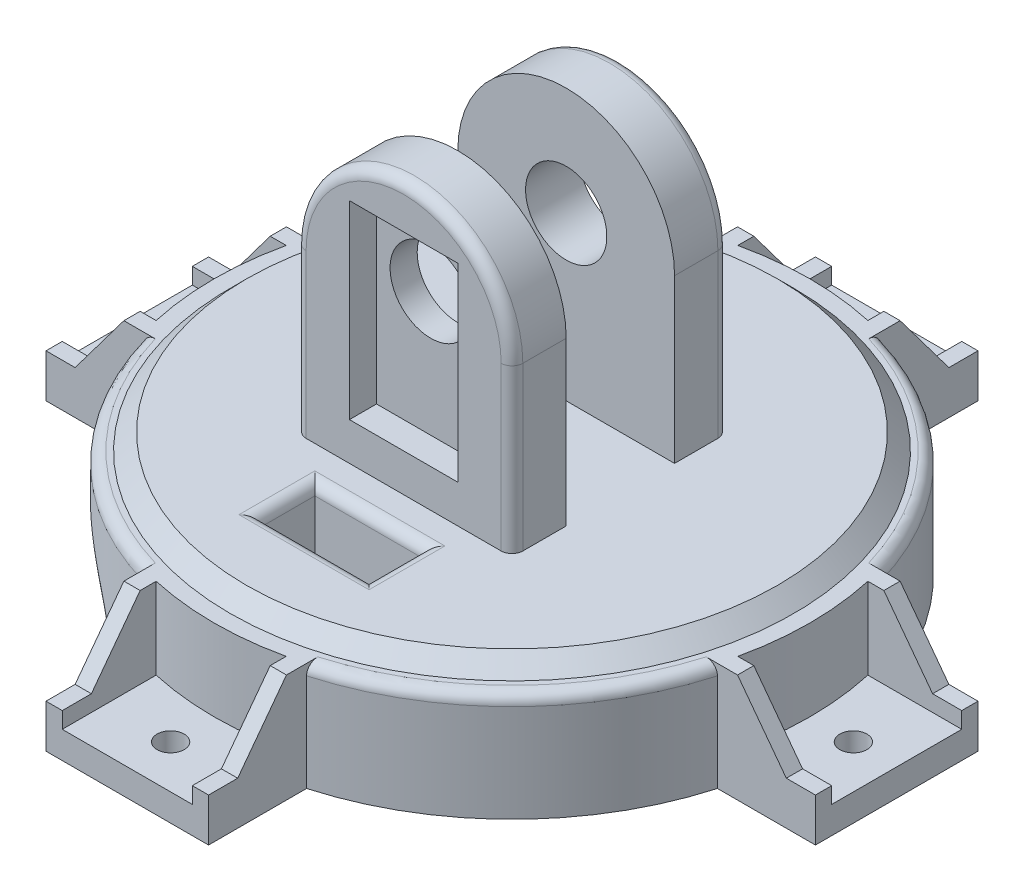
SolidWorks part; units mm, degrees
material "PPE"
ref_plane "Front Plane" through (0, 0, 0) normal (0, 0, 1) x (1, 0, 0)
ref_plane "Top Plane" through (0, 0, 0) normal (0, 1, 0) x (1, 0, 0)
ref_plane "Right Plane" through (0, 0, 0) normal (1, 0, 0) x (0, 0, -1)
sketch "Sketch1" plane through (0, 0, 0) normal (0, 1, 0) x (1, 0, 0)
  circle A0 centre (0, 0) radius 55
  dimension "D1" = 110
extrude "Boss-Extrude1" add sketch "Sketch1" along normal blind 20 contours A0
sketch "Sketch2" plane through (0, 20, 0) normal (0, 1, 0) x (1, 0, 0)
  circle A0 centre (0, 0) radius 54
  dimension "D1" = 108
extrude "Boss-Extrude3" add sketch "Sketch2" along normal blind 3
chamfer "Chamfer2" distance 5 angle 45 1 edges at (0, 23, 54)
sketch "Sketch9" plane through (0, 20, 0) normal (0, 1, 0) x (1, 0, 0)
  line L0 (0, 0) -> (0, -96.0857) construction
  line L1 (-15, -46) -> (15, -46)
  line L2 (15, -46) -> (15, -71)
  line L3 (15, -71) -> (-15, -71)
  line L4 (-15, -46) -> (-15, -71)
  point P8 (0, -71)
  point P9 (0, -46)
  dimension "D1" = 46
  dimension "D2" = 25
  dimension "D3" = 15
extrude "Boss-Extrude5" add sketch "Sketch9" against normal up to surface (20 mm away) contours L3 L4 L1 L2 up to face at (0, 0, 55)
sketch "Sketch14" plane through (0, 20, 0) normal (0, 1, 0) x (1, 0, 0)
  line L0 (12, -53.6749) -> (12, -203.6749)
  line L1 (12, -203.6749) -> (-12, -203.6749)
  line L2 (-12, -203.6749) -> (-12, -53.6749)
  line L3 (15, -52.915) -> (15, -71) construction
  line L4 (-15, -52.915) -> (-15, -71) construction
  arc A0 (15, -52.915) -> (-15, -52.915) centre (0, 0) ccw construction
  arc A1 (-12, -53.6749) -> (12, -53.6749) centre (0, 0) ccw
  dimension "D1" = 3
  dimension "D2" = 3
  dimension "D3" = 150
extrude "Cut-Extrude1" cut sketch "Sketch14" against normal blind 15
sketch "Sketch15" plane through (-15, 0, 0) normal (-1, 0, 0) x (0, 0, 1)
  line L0 (56.6264, 20) -> (65.6264, 8)
  line L1 (52.915, 20) -> (71, 20) construction
  line L2 (65.6264, 8) -> (71, 8)
  line L3 (71, 0) -> (71, 20) construction
  dimension "D1" = 12
  dimension "D2" = 15
  dimension "D3" = 14.3736
extrude "Cut-Extrude2" cut sketch "Sketch15" against normal through all and the other way through all
sketch "Sketch16" plane through (0, 5, 0) normal (0, 1, 0) x (1, 0, 0)
  line L0 (0, 0) -> (0, -99.4837) construction
  circle A1 centre (0, -63) radius 2.5
  dimension "D1" = 5
  dimension "D2" = 63
extrude "Cut-Extrude3" cut sketch "Sketch16" against normal through all
pattern_circular "CirPattern4" count 4 over 360 about axis through (0, 23, 0) along (0, 1, 0) of "Cut-Extrude3", "Cut-Extrude1", "Boss-Extrude5", "Cut-Extrude2", "Boss-Extrude1"
sketch "Sketch24" plane through (0, 23, 0) normal (0, 1, 0) x (1, 0, 0)
  circle A0 centre (0, 0) radius 46.3294
  dimension "D1" = 92.6588
sketch "Sketch25" plane through (0, 23, 0) normal (0, 1, 0) x (1, 0, 0)
  line L0 (0, 0) -> (72.6186, 0) construction
  line L1 (72.6186, 0) -> (-65.5, 0) construction
  line L2 (0, 0) -> (0, -145.4526) construction
  line L3 (0, 0) -> (0, 132.6732) construction
  line L4 (-20, -20) -> (-20, -10)
  line L5 (-20, 20) -> (20, 20)
  line L6 (-20, 20) -> (-20, 10)
  line L7 (-20, 10) -> (20, 10)
  line L8 (20, 20) -> (20, 10)
  line L9 (-20, 20) -> (20, 10) construction
  line L10 (-20, 10) -> (20, 20) construction
  line L11 (-20, -20) -> (20, -20)
  line L12 (20, -20) -> (20, -10)
  line L13 (-20, -10) -> (20, -10)
  circle A0 centre (-63, 0) radius 2.5 construction
  point P3 (0, 15)
  dimension "D1" = 10
  dimension "D2" = 40
  dimension "D3" = 15
extrude "Boss-Extrude6" add sketch "Sketch25" along normal blind 50 contours L6 L5 L8 L7 | L4 L13 L12 L11
sketch "Sketch26" plane through (0, 0, -20) normal (0, 0, -1) x (-1, 0, 0)
  line L0 (0, 0) -> (0, 83.8604) construction
  line L1 (20, 73) -> (-20, 73) construction
  line L2 (0, 53) -> (-69.1656, 53) construction
  line L3 (-69.1656, 53) -> (71.7644, 53) construction
  line L4 (-20, 53) -> (-20, 73)
  line L5 (-20, 73) -> (20, 73)
  line L6 (20, 73) -> (20, 53)
  line L7 (20, 53) -> (20, 73)
  arc A0 (20, 53) -> (-20, 53) centre (0, 53) ccw
  point P3 (-20, 23)
  line M4 (20, 23) -> (20, 73)
  line M5 (20, 73) -> (-20, 73)
  line M6 (-20, 73) -> (-20, 23)
  dimension "D1" = 40
  dimension "D2" = 20
extrude "Cut-Extrude4" cut sketch "Sketch26" against normal blind 50 contours A0 L5 M6 | A0 M4 M5 region at (-15.5326, 68.5326, -20) region at (15.5326, 68.5326, -20)
sketch "Sketch27" plane through (0, 0, 0) normal (0, -1, 0) x (1, 0, 0)
  circle A0 centre (0, 0) radius 40
  dimension "D1" = 80
extrude "Cut-Extrude5" cut sketch "Sketch27" against normal blind 10
sketch "Sketch28" plane through (0, 0, 0) normal (0, -1, 0) x (1, 0, 0)
  circle A0 centre (0, 0) radius 50
  dimension "D1" = 100
extrude "Cut-Extrude6" cut sketch "Sketch28" against normal blind 5
sketch "Sketch29" plane through (0, 0, 20) normal (0, 0, 1) x (1, 0, 0)
  line L0 (0, 0) -> (0, 91.8175) construction
  circle A0 centre (0, 53) radius 7.5
  arc A1 (20, 53) -> (-20, 53) centre (0, 53) ccw construction
  point P5 (0, 73)
  dimension "D1" = 15
  dimension "D2" = 20
extrude "Cut-Extrude7" cut sketch "Sketch29" against normal blind 49
sketch "Sketch30" plane through (0, 0, 20) normal (0, 0, 1) x (1, 0, 0)
  line L0 (0, 0) -> (0, 88.298) construction
  line L1 (10, 65) -> (-10, 65)
  line L2 (-10, 65) -> (-10, 30)
  line L3 (-10, 30) -> (10, 30)
  line L4 (10, 65) -> (10, 30)
  point P8 (0, 30)
  point P9 (0, 65)
  dimension "D1" = 10
  dimension "D2" = 35
  dimension "D3" = 30
extrude "Cut-Extrude8" cut sketch "Sketch30" against normal blind 5
fillet "Fillet1" radius 2 6 edges at (-20, 38, 20) (20, 38, 20) (-20, 38, -20) (20, 38, -20) (0, 73, 20) (0, 73, -20)
sketch "Sketch31" plane through (0, 23, 0) normal (0, 1, 0) x (1, 0, 0)
  line L0 (0, 0) -> (0, -82.677) construction
  line L2 (-10, -36.3875) -> (10, -36.3875)
  line L3 (-10, -36.3875) -> (-10, -26.3875)
  line L4 (-10, -26.3875) -> (10, -26.3875)
  line L5 (10, -36.3875) -> (10, -26.3875)
  line L6 (-10, -36.3875) -> (10, -26.3875) construction
  line L7 (-10, -26.3875) -> (10, -36.3875) construction
  point P3 (0, -31.3875)
  dimension "D1" = 10
  dimension "D2" = 20
extrude "Cut-Extrude9" cut sketch "Sketch31" against normal up to next
fillet "Fillet2" radius 2 4 edges at (10, 23, 31.3875) (0, 23, 36.3875) (-10, 23, 31.3875) (0, 23, 26.3875)
sketch "Sketch32" plane through (0, 0, 0) normal (1, 0, 0) x (0, 0, -1)
  line L0 (-52.915, 0) -> (-15, 0) construction
  circle A0 centre (-35, 0) radius 10
  dimension "D1" = 20
  dimension "D2" = 35
extrude "Cut-Extrude11" cut sketch "Sketch32" against normal up to next
fillet "Fillet3" radius 2 5 edges at (38.8909, 20, -38.8909) (38.8909, 20, 38.8909) (-38.8909, 20, 38.8909) (-38.8909, 20, -38.8909) (-43.0455, 9.9707, 34.2357)
ref_plane "Plane1" through (0, 0, 0) normal (0, 0, -1) x (-1, 0, 0)
sketch "Sketch34" plane through (0, 0, 0) normal (0, 0, -1) x (-1, 0, 0)
  line L0 (0, 0) -> (0, 97.5219) construction
sketch "Sketch37" plane through (0, 0, 0) normal (0, 0, -1) x (-1, 0, 0)
  line L0 (0, 0) -> (0, 53) construction
  line L1 (0, 0) -> (0, 97.5219) construction
  dimension "D1" = 53
sketch "Sketch38" plane through (0, 0, 0) normal (0, 0, -1) x (-1, 0, 0)
  point P0 (0, 53)
